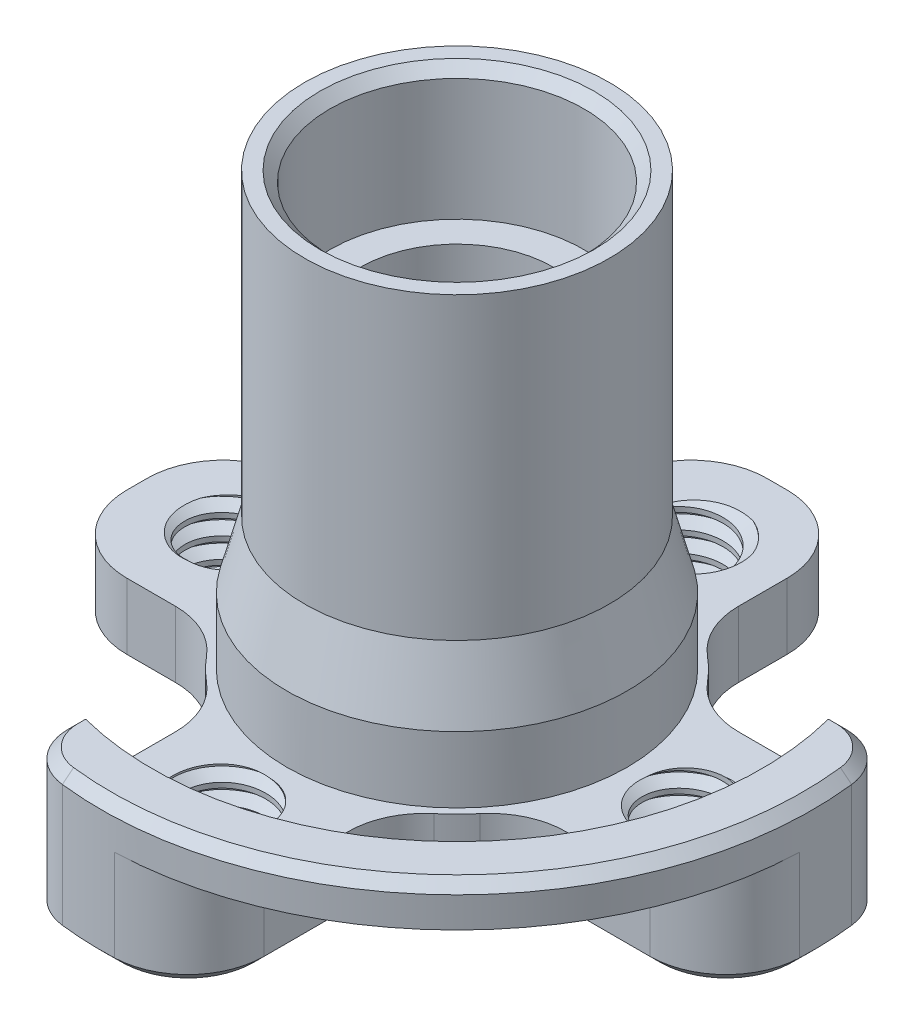
SolidWorks part; units mm, degrees
note: The reader was unsure of these and kept them because the rebuilt part matched: shared geometry of "Sketch4<3>".
material "6061-T6 (SS)"
ref_plane "Front Plane" through (0, 0, 0) normal (0, 0, 1) x (1, 0, 0)
ref_plane "Top Plane" through (0, 0, 0) normal (0, 1, 0) x (1, 0, 0)
ref_plane "Right Plane" through (0, 0, 0) normal (1, 0, 0) x (0, 0, -1)
sketch "Sketch1" plane through (0, 0, 0) normal (0, 0, 1) x (1, 0, 0)
  line L0 (-2.5, 7.4) -> (-2.5, 10)
  line L1 (-2.5, 10) -> (-3, 10)
  line L2 (-3, 10) -> (-3, 4.1062)
  line L3 (-3, 4.1062) -> (-3.35, 2.8)
  line L7 (-3.35, 2.8) -> (-7, 2.8)
  line L8 (-7, 2.8) -> (-7, 0)
  line L9 (-7, 0) -> (-2.5, 0)
  line L10 (-2.5, 0) -> (-2.5, 2.6)
  line L11 (-2.5, 2.6) -> (-1.9, 2.6)
  line L12 (-1.9, 2.6) -> (-1.9, 7.4)
  line L13 (-1.9, 7.4) -> (-2.5, 7.4)
  line L14 (0, 10) -> (0, 0) construction
  dimension "D1" = 14
  dimension "D2" = 5
  dimension "D3" = 2.8
  dimension "D4" = 6
  dimension "D5" = 3.8
  dimension "D6" = 10
  dimension "D7" = 2.6
  dimension "D8" = 105
  dimension "D9" = 6.7
revolve "Revolve1" add sketch "Sketch1" angle 360 about L14
sketch "Sketch2" plane through (0, 0, 0) normal (0, 1, 0) x (1, 0, 0)
  circle A0 centre (0, 0) radius 6
  circle A1 centre (0, 0) radius 3.35
  circle A2 centre (0, 0) radius 3.35 construction
  dimension "D1" = 12
extrude "Cut-Extrude1" cut sketch "Sketch2" against normal offset from surface (1.3 mm away) 1.5 from surface at 2.8 up to face at (-2.5, 0, 0) starting at face at (-7, 2.8, 0)
sketch "Sketch3" plane through (0, 0, 0) normal (0, 1, 0) x (1, 0, 0)
  circle A0 centre (0, 4.5) radius 0.8
  circle A1 centre (4.5, 0) radius 0.8
  circle A2 centre (0, -4.5) radius 0.8
  circle A3 centre (-4.5, 0) radius 0.8
  point P12 (0, 0)
  dimension "D1" = 4.5
  dimension "D2" = 1.6
  dimension "D3" = 4
extrude "Cut-Extrude2" cut sketch "Sketch3" along normal up to next
sketch "Sketch4" plane through (0, 0, 0) normal (0, 1, 0) x (1, 0, 0)
  line L0 (-1.7, 6.7904) -> (-1.7, 3.0594)
  line L1 (1.7, 6.7904) -> (1.7, 3.0594)
  line L2 (6.7904, 1.7) -> (3.0594, 1.7)
  line L3 (0, 0) -> (0, 7) construction
  line L4 (6.7904, -1.7) -> (3.0594, -1.7)
  line L5 (1.7, -6.7904) -> (1.7, -3.0594)
  line L6 (-1.7, -6.7904) -> (-1.7, -3.0594)
  line L7 (-6.7904, -1.7) -> (-3.0594, -1.7)
  line L8 (-6.7904, 1.7) -> (-3.0594, 1.7)
  circle A0 centre (0, 0) radius 3.5
  circle A1 centre (0, 0) radius 7 construction
  circle A2 centre (0, 0) radius 7
  point P27 (0, 0)
  dimension "D1" = 3.4
  dimension "D3" = 7
  dimension "D2" = 4
extrude "Cut-Extrude3" cut sketch "Sketch4" along normal blind 2 contours L5 A2 L4 A0
extrude "Cut-Extrude4" cut sketch "Sketch4<3>" along normal up to next contours L0 A2 L8 A0 | L2 A2 L1 A0 | L7 A2 L6 A0
sketch "Sketch4<3>" plane through (0, 0, 0) normal (0, 1, 0) x (1, 0, 0) same geometry as "Sketch4"
sketch "Sketch5" plane through (0, 0, 0) normal (0, 1, 0) x (1, 0, 0)
  line L6 (-6.7904, -1.7) -> (-5.7541, -1.7) construction
  line L7 (-5.7541, 1.7) -> (-6.7904, 1.7) construction
  line L8 (1.7, 5.7541) -> (1.7, 6.7904) construction
  line L9 (-1.7, 6.7904) -> (-1.7, 5.7541) construction
  line L10 (-6.7904, -1.7) -> (-5.7541, -1.7)
  line L11 (-5.7541, 1.7) -> (-6.7904, 1.7)
  line L12 (1.7, 5.7541) -> (1.7, 6.7904)
  line L13 (-1.7, 6.7904) -> (-1.7, 5.7541)
  arc A0 (-5.7541, 1.7) -> (-5.7541, -1.7) centre (0, 0) ccw construction
  arc A1 (-6.7904, 1.7) -> (-6.7904, -1.7) centre (0, 0) ccw construction
  arc A2 (1.7, 5.7541) -> (-1.7, 5.7541) centre (0, 0) ccw construction
  arc A3 (1.7, 6.7904) -> (-1.7, 6.7904) centre (0, 0) ccw construction
  arc A4 (-5.7541, 1.7) -> (-5.7541, -1.7) centre (0, 0) ccw
  arc A5 (-6.7904, 1.7) -> (-6.7904, -1.7) centre (0, 0) ccw
  arc A6 (1.7, 5.7541) -> (-1.7, 5.7541) centre (0, 0) ccw
  arc A7 (1.7, 6.7904) -> (-1.7, 6.7904) centre (0, 0) ccw
extrude "Cut-Extrude5" cut sketch "Sketch5" along normal up to next (2.8 mm away) from surface at 1.5 starting at face at (0.8, 1.5, -4.5)
sketch "Sketch6" plane through (0, 0, 0) normal (0, 1, 0) x (1, 0, 0)
  line L0 (-1.7, 6.3) -> (1.7, 6.3)
  line L1 (-1.7, 6.7904) -> (-1.7, 3.0594) construction
  line L2 (1.7, 6.7904) -> (1.7, 3.0594) construction
  line L3 (1.7, 6.3) -> (1.7, 6.7904)
  line L4 (-1.7, 6.7904) -> (-1.7, 6.3)
  line L5 (-6.3, -1.7) -> (-6.3, 1.7)
  line L6 (-6.7904, -1.7) -> (-6.3, -1.7)
  line L7 (-6.3, 1.7) -> (-6.7904, 1.7)
  line L8 (0, 0) -> (1.7, 6.3) construction
  line L9 (0, 0) -> (-6.3, 1.7) construction
  arc A0 (1.7, 6.7904) -> (-1.7, 6.7904) centre (0, 0) ccw construction
  arc A1 (1.7, 6.7904) -> (-1.7, 6.7904) centre (0, 0) ccw
  arc A2 (-6.7904, 1.7) -> (-6.7904, -1.7) centre (0, 0) ccw
  point P17 (0, 0)
  dimension "D1" = 6.3
  dimension "D3" = 270
  dimension "D2" = 2
extrude "Cut-Extrude6" cut sketch "Sketch6" along normal up to next
fillet "Fillet1" radius 1.5 14 edges at (3.0594, 0.75, -1.7) (1.7, 0.75, -3.0594) (-1.7, 0.75, -3.0594) (-3.0594, 0.75, -1.7) (-1.7, 0.75, 3.0594) (-3.0594, 0.75, 1.7) (1.7, 1, 6.7904) (6.7904, 1, 1.7) (1.7, 0.75, -6.3) (-1.7, 0.75, -6.3) (-6.3, 0.75, 1.7) (-6.3, 0.75, -1.7) (3.0594, 0.75, 1.7) (1.7, 0.75, 3.0594)
fillet "Fillet2" radius 1 2 edges at (6.7904, 1.4, -1.7) (-1.7, 1.4, 6.7904)
chamfer "Chamfer1" distance 0.2 angle 45 39 edges at (2.4749, 0, -2.4749) (1.8417, 0, -3.2055) (3.2055, 0, -1.8417) (1.7, 0, -4.3209) (4.9005, 0, -1.7) (1.2607, 0, -5.8607) (6.6236, 0, -1.4472) (0, 0, -6.3) (6.9943, 0, -0.2819) (-1.2607, 0, -5.8607) (6.5376, 0, 1.2798) (-1.7, 0, -4.3209) (4.6691, 0, 1.7) (-1.8417, 0, -3.2055) (3.2055, 0, 1.8417) (-2.4749, 0, -2.4749) (2.4749, 0, 2.4749) (-3.2055, 0, -1.8417) (1.8417, 0, 3.2055) (-4.3209, 0, -1.7) (1.7, 0, 4.6691) (-5.8607, 0, -1.2607) (1.2798, 0, 6.5376) (-6.3, 0, 0) (-0.2819, 0, 6.9943) (-5.8607, 0, 1.2607) (-1.4472, 0, 6.6236) (-4.3209, 0, 1.7) (-1.7, 0, 4.9005) (-3.2055, 0, 1.8417) (-1.8417, 0, 3.2055) (-2.4749, 0, 2.4749) (-1.7, 2.8, 5.8566) (5.8566, 2.8, -1.7) (-1.4472, 2.8, 6.6236) (6.6236, 2.8, -1.4472) (4.9497, 2.8, 4.9497) (-2.5, 10, 0) (-2.5, 0, 0)
thread "Thread1" pitch 0.4 start angle 0, offset 0.4, length 0, pitch 0.4, diameter 1.6
ref_plane "Plane1" through (-3.7, -0.4, 0) normal (0, 0, 1) x (1, 0, 0)
sketch "Thread Profile1" plane through (-3.7, -0.4, 0) normal (0, 0, 1) x (1, 0, 0)
  line L0 (0, 0) -> (0, 0.4) construction
  line L1 (0, 0) -> (0.2165, 0.125)
  line L2 (0.2165, 0.125) -> (0.2165, 0.175)
  line L3 (0.2165, 0.175) -> (0, 0.3)
  line L4 (0.2165, 0.15) -> (0, 0.15) construction
  line L11 (0, 0) -> (0, 0.3)
  point P2 (0, 0)
  dimension "Pitch" = 0.4
  dimension "Profile_Angle" = 60
  dimension "Profile_Land" = 0.05
  dimension "Profile_Height" = 0.2165
pattern_circular "CirPattern1" count 4 over 360 about axis through (0, 10, 0) along (0, 1, 0) of "Thread1"
